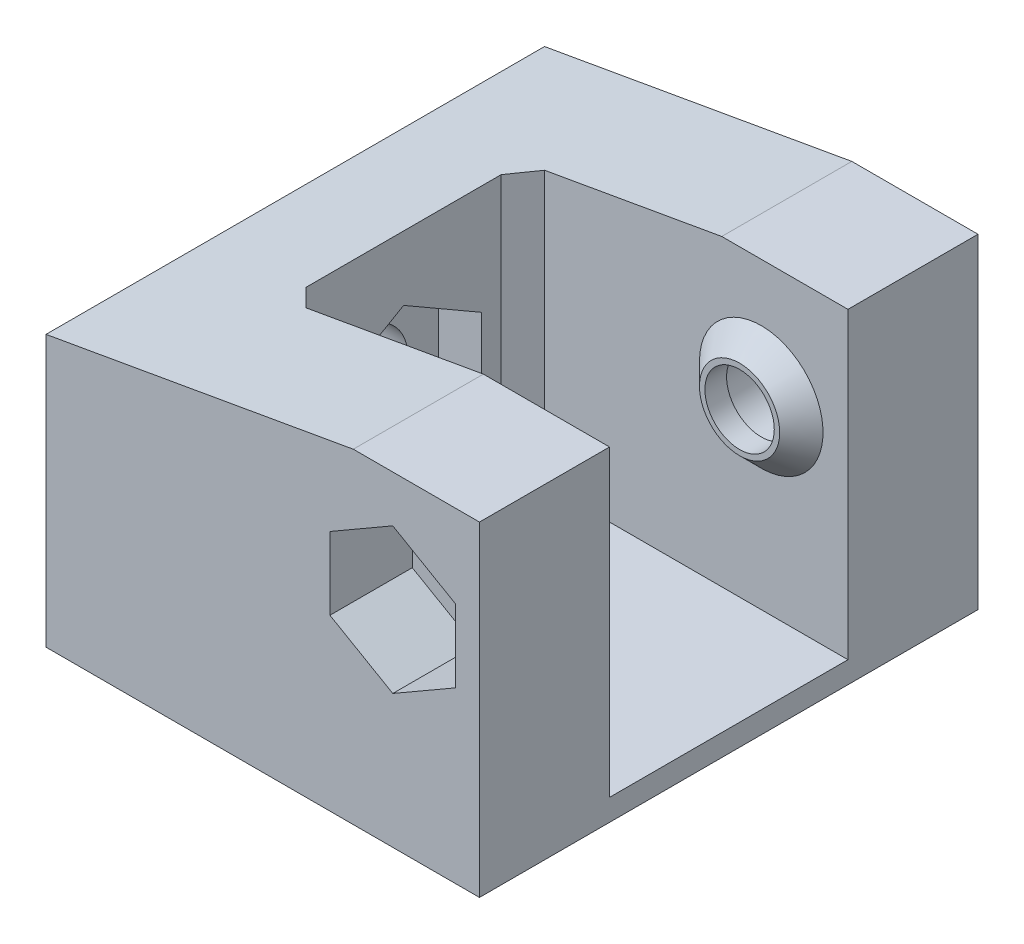
SolidWorks part; units mm, degrees
ref_plane "Front Plane" through (0, 0, 0) normal (0, 0, 1) x (1, 0, 0)
ref_plane "Top Plane" through (0, 0, 0) normal (0, 1, 0) x (1, 0, 0)
ref_plane "Right Plane" through (0, 0, 0) normal (1, 0, 0) x (0, 0, -1)
sketch "Sketch1" plane through (0, 0, 0) normal (1, 0, 0) x (0, 0, -1)
  line L1 (0, 0) -> (23, 0)
  line L2 (0, 0) -> (0, 15)
  line L3 (0, 15) -> (23, 15)
  line L4 (23, 0) -> (23, 15)
  dimension "D1" = 23
  dimension "D2" = 15
extrude "Boss-Extrude1" add sketch "Sketch1" along normal blind 20
sketch "Sketch2" plane through (20, 0, 0) normal (1, 0, 0) x (0, 0, -1)
  line L0 (11.5, 15) -> (11.5, 0) construction
  line L1 (6, 15) -> (17, 15)
  line L2 (6, 15) -> (6, 0)
  line L3 (6, 0) -> (17, 0)
  line L4 (17, 15) -> (17, 0)
  line L5 (0, 0) -> (23, 0) construction
  line L8 (23, 15) -> (0, 15) construction
  line L9 (11.5, 15) -> (11.5, 0) construction
  dimension "D1" = 11
extrude "Cut-Extrude1" cut sketch "Sketch2" against normal offset from surface (15 mm away) 5 up to face at (0, 7.5, -11.5)
sketch "Sketch3" plane through (0, 0, -23) normal (0, 0, -1) x (-1, 0, 0)
  line L1 (-20, 0) -> (-20, 15) construction
  line L2 (-20, 0) -> (0, 0) construction
  circle A0 centre (-16, 9.5) radius 1.7
  dimension "D3" = 3.4
  dimension "D1" = 9.5
  dimension "D2" = 4
extrude "Cut-Extrude2" cut sketch "Sketch3" against normal through all both and the other way through all
chamfer "Chamfer1" distance 2.5 angle 80 1 edges at (0, 15, -11.5) first distance on face at (0, 7.5, -11.5)
sketch "Sketch4" plane through (0, 0, 0) normal (-1, 0, 0) x (0, 0, 1)
  line L0 (-11.5, 12.5) -> (-11.5, 0) construction
  line L1 (0, 12.5) -> (-23, 12.5) construction
  line L2 (0, 0) -> (-23, 0) construction
  line L3 (-23, 6.25) -> (0, 6.25) construction
  line L4 (-23, 0) -> (-23, 12.5) construction
  line L5 (0, 12.5) -> (0, 0) construction
  circle A0 centre (-11.5, 6.25) radius 2.2
  dimension "D1" = 4.4
extrude "Cut-Extrude3" cut sketch "Sketch4" against normal blind 10
sketch "Sketch5" plane through (5, 0, 0) normal (1, 0, 0) x (0, 0, -1)
  line L1 (7.9, 8.3285) -> (7.9, 4.1715)
  line L2 (7.9, 4.1715) -> (11.5, 2.0931)
  line L3 (11.5, 2.0931) -> (15.1, 4.1715)
  line L4 (15.1, 4.1715) -> (15.1, 8.3285)
  line L5 (15.1, 8.3285) -> (11.5, 10.4069)
  line L6 (11.5, 10.4069) -> (7.9, 8.3285)
  circle A0 centre (11.5, 6.25) radius 3.6 construction
  dimension "D1" = 7.2
extrude "Cut-Extrude4" cut sketch "Sketch5" against normal blind 2
sketch "Sketch6" plane through (0, 0, -23) normal (0, 0, -1) x (-1, 0, 0)
  circle A0 centre (-16, 9.5) radius 3.25
  dimension "D1" = 6.5
extrude "Cut-Extrude5" cut sketch "Sketch6" against normal blind 2.5
sketch "Sketch7" plane through (0, 0, 0) normal (0, 0, 1) x (1, 0, 0)
  line L1 (13.1, 11.1743) -> (13.1, 7.8257)
  line L2 (13.1, 7.8257) -> (16, 6.1514)
  line L3 (16, 6.1514) -> (18.9, 7.8257)
  line L4 (18.9, 7.8257) -> (18.9, 11.1743)
  line L5 (18.9, 11.1743) -> (16, 12.8486)
  line L6 (16, 12.8486) -> (13.1, 11.1743)
  circle A0 centre (16, 9.5) radius 2.9 construction
  dimension "D1" = 5.8
extrude "Cut-Extrude6" cut sketch "Sketch7" against normal blind 3.8
sketch "Sketch8" plane through (0, 0, -17) normal (0, 0, 1) x (1, 0, 0)
  circle A0 centre (16, 9.5) radius 1.85
  circle A1 centre (16, 9.5) radius 1.6009
  dimension "D1" = 3.7
  dimension "D2" = 3.2017
sketch "Sketch9" plane through (0, 0, -6) normal (0, 0, -1) x (-1, 0, 0)
  circle A0 centre (-16, 9.5) radius 1.6
  circle A1 centre (-16, 9.5) radius 1.85
  dimension "D1" = 3.7
  dimension "D2" = 3.2
chamfer "Chamfer3" distance 1 angle 45 2 edges at (5, 6.6908, -6) (5, 6.6908, -17)
extrude "Boss-Extrude2" add sketch "Sketch9" along normal blind 1
extrude "Boss-Extrude3" add sketch "Sketch8" along normal blind 1
chamfer "Chamfer4" distance 1 angle 45 2 edges at (16, 7.65, -6) (14.15, 9.5, -17)
sketch "Sketch10" plane through (0, 0, -23) normal (0, 0, -1) x (-1, 0, 0)
  line L0 (-20, 0) -> (-20, 15) construction
  line L1 (-20, 1) -> (0, 1)
  line L2 (-20, 1) -> (-20, 0)
  line L3 (-20, 0) -> (0, 0)
  line L4 (0, 1) -> (0, 0)
  dimension "D1" = 1
extrude "Boss-Extrude4" add sketch "Sketch10" against normal up to surface (23 mm away) up to face at (16, 9.5, 0)
